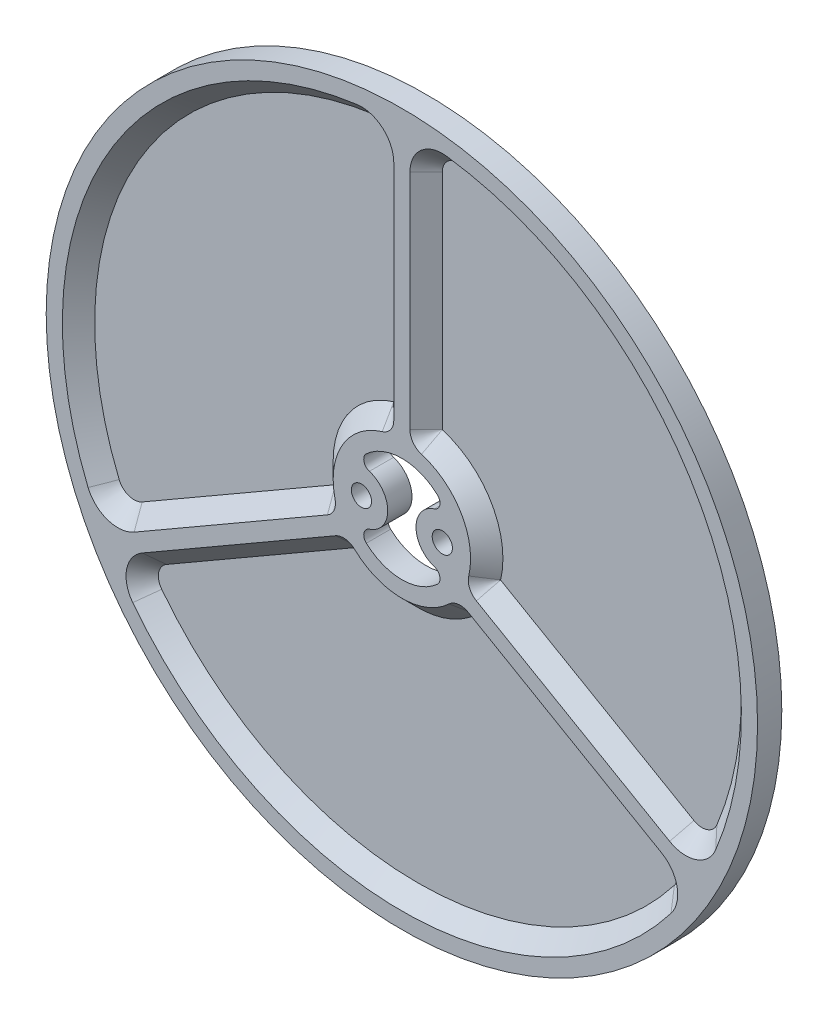
SolidWorks part; units mm, degrees
material "ABS"
ref_plane "Front Plane" through (0, 0, 0) normal (0, 0, 1) x (1, 0, 0)
ref_plane "Top Plane" through (0, 0, 0) normal (0, 1, 0) x (1, 0, 0)
ref_plane "Right Plane" through (0, 0, 0) normal (1, 0, 0) x (0, 0, -1)
sketch "Sketch1" plane through (0, 0, 0) normal (0, 0, 1) x (1, 0, 0)
  circle A0 centre (0, 0) radius 44
  circle A1 centre (0, 0) radius 42
  circle A5 centre (0, 0) radius 8.5
  dimension "D1" = 84
  dimension "D3" = 17
  dimension "D2" = 2
extrude "Boss-Extrude1" add sketch "Sketch1" along normal mid plane 3 contours A0 A1 | A5 region at (-42.7555, 0, 0) region at (0, 0, 0)
extrude "Boss-Extrude3" add sketch "Sketch1<3>" along normal blind 1 from surface contours A1 A5 region at (-40.8121, 0, 0) starting at face at (42, 0, -1.5)
sketch "Sketch1<3>" plane through (0, 0, 0) normal (0, 0, 1) x (1, 0, 0) same geometry as "Sketch1"
sketch "Sketch2" plane through (0, 0, 0) normal (0, 0, 1) x (1, 0, 0)
  line L0 (-1, 41.9881) -> (-1, 0)
  line L1 (-1, 0) -> (1, 0)
  line L2 (1, 0) -> (1, 41.9881)
  circle A0 centre (0, 0) radius 42 construction
  arc A1 (1, 41.9881) -> (-1, 41.9881) centre (0, 0) ccw
  arc A2 (-1, 41.9881) -> (1, 41.9881) centre (0, 0) ccw construction
  point P2 (0, 42)
  dimension "D1" = 2
extrude "Boss-Extrude2" add sketch "Sketch2" along normal mid plane 3
pattern_circular "CirPattern1" count 3 over 360 about axis through (0, 0, 1.5) along (0, 0, 1) of "Boss-Extrude2"
sketch "Sketch3" plane through (0, 0, 0) normal (0, 0, 1) x (1, 0, 0)
  line L0 (-5, 0) -> (5, 0) construction
  circle A0 centre (-5, 0) radius 1.25
  circle A1 centre (5, 0) radius 1.25
  point P4 (0, 0)
  dimension "D1" = 2.5
  dimension "D2" = 10
extrude "Cut-Extrude1" cut sketch "Sketch3" against normal through all both and the other way through all
sketch "Sketch5" plane through (0, 0, 0) normal (0, 0, 1) x (1, 0, 0)
  circle A14 centre (-5, 0) radius 3.25
  arc A15 (-5.6688, -3.1805) -> (-5.6688, 3.1805) centre (-5, 0) ccw
  arc A16 (-5.6688, -3.1805) -> (5.6688, -3.1805) centre (0, 0) ccw
  circle A17 centre (5, 0) radius 3.25
  arc A18 (5.6688, 3.1805) -> (5.6688, -3.1805) centre (5, 0) ccw
  arc A20 (-5.6688, 3.1805) -> (-5.6688, -3.1805) centre (-5, 0) ccw construction
  arc A21 (-5.6688, 3.1805) -> (-5.6688, -3.1805) centre (0, 0) ccw construction
  arc A22 (5.6688, 3.1805) -> (-5.6688, 3.1805) centre (0, 0) ccw
  arc A23 (5.6688, -3.1805) -> (5.6688, 3.1805) centre (0, 0) ccw construction
  arc A24 (5.6688, -3.1805) -> (5.6688, 3.1805) centre (5, 0) ccw construction
  arc A25 (-6.8101, -5.0865) -> (6.8101, -5.0865) centre (0, 0) ccw construction
  dimension "D2" = 2
  dimension "D1" = 2
extrude "Cut-Extrude2" cut sketch "Sketch5" against normal through all both and the other way through all
fillet "Fillet1" radius 1 4 edges at (-5.6688, 3.1805, 0) (-5.6688, -3.1805, 0) (5.6688, -3.1805, 0) (5.6688, 3.1805, 0)
fillet "Fillet2" radius 4 6 edges at (35.8628, -21.8601, 0.5) (36.8628, -20.128, 0.5) (1, 41.9881, 0.5) (-1, 41.9881, 0.5) (-35.8628, -21.8601, 0.5) (-36.8628, -20.128, 0.5)
fillet "Fillet3" radius 2 6 edges at (1, 8.441, 0.5) (7.8101, -3.3545, 0.5) (6.8101, -5.0865, 0.5) (-6.8101, -5.0865, 0.5) (-1, 8.441, 0.5) (-7.8101, -3.3545, 0.5)
chamfer "Chamfer1" distance 2 angle 45 24 edges at (34.0464, -22.3867, -0.5) (0, -42, -0.5) (-34.0464, -22.3867, -0.5) (-20.1685, -12.799, -0.5) (-6.9809, -5.6429, -0.5) (0, -8.5, -0.5) (6.9809, -5.6429, -0.5) (20.1685, -12.799, -0.5) (2.3642, 40.6784, -0.5) (36.3731, 21, -0.5) (36.4106, -18.2917, -0.5) (21.1685, -11.067, -0.5) (8.3773, -3.2242, -0.5) (7.3612, 4.25, -0.5) (1.3964, 8.8671, -0.5) (1, 23.866, -0.5) (-8.3773, -3.2242, -0.5) (-21.1685, -11.067, -0.5) (-36.4106, -18.2917, -0.5) (-36.3731, 21, -0.5) (-2.3642, 40.6784, -0.5) (-1, 23.866, -0.5) (-1.3964, 8.8671, -0.5) (-7.3612, 4.25, -0.5)
equation "\"bracket_thickness\"= 3mm"
equation "\"rib_width\"= 2mm"
equation "\"D2@Sketch1\"=\"rib_width\""
equation "\"D1@Boss-Extrude1\"=\"bracket_thickness\""
equation "\"D1@Sketch2\"=\"rib_width\""
equation "\"D1@Boss-Extrude2\"=\"bracket_thickness\""
equation "\"D3@Sketch1\"=\"rib_width\"+15"
equation "\"D1@Sketch5\"=\"rib_width\""
equation "\"D2@Sketch5\"=\"rib_width\""
equation "\"D3@Sketch5\"=\"rib_width\""
